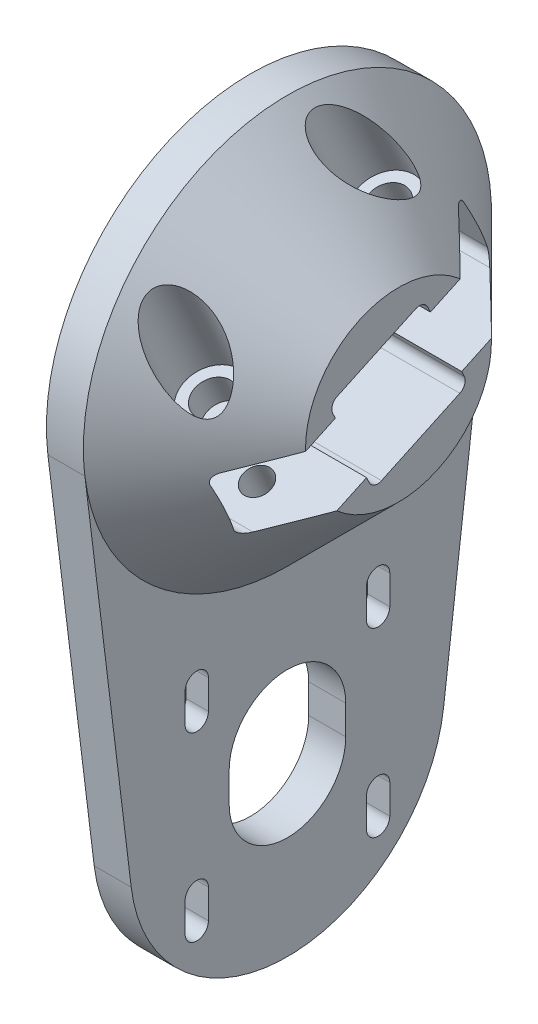
SolidWorks part; units mm, degrees
ref_plane "Front Plane" through (0, 0, 0) normal (0, 0, 1) x (1, 0, 0)
ref_plane "Top Plane" through (0, 0, 0) normal (0, 1, 0) x (1, 0, 0)
ref_plane "Right Plane" through (0, 0, 0) normal (1, 0, 0) x (0, 0, -1)
sketch "Sketch1" plane through (0, 0, 0) normal (1, 0, 0) x (0, 0, -1)
  line L0 (4.3532, 11.9603) -> (-11.9603, 4.3532)
  line L1 (4.3532, 11.9603) -> (11.9603, -4.3532)
  line L2 (-11.9603, 4.3532) -> (-4.3532, -11.9603)
  line L3 (11.9603, -4.3532) -> (-4.3532, -11.9603)
  line L4 (4.3532, 11.9603) -> (-4.3532, -11.9603) construction
  line L5 (-11.9603, 4.3532) -> (11.9603, -4.3532) construction
  line L6 (0, 0) -> (0, -63.5) construction
  line L7 (-34.7419, -4.2424) -> (-26.8009, -69.2727)
  line L8 (26.8009, -69.2727) -> (34.7419, -4.2424)
  line L9 (0, -63.5) -> (0, -103.9417) construction
  arc A0 (34.7419, -4.2424) -> (-34.7419, -4.2424) centre (0, 0) ccw
  arc A1 (-26.8009, -69.2727) -> (26.8009, -69.2727) centre (0, -66) ccw
  dimension "D1" = 2.5
  dimension "D2" = 70
  dimension "D6" = 63.5
  dimension "D7" = 27
  dimension "D8" = 0
  dimension "D3" = 18
  dimension "D4" = 18
  dimension "D5" = 25
extrude "Boss-Extrude1" add sketch "Sketch1" along normal blind 6.35 contours L7 A0 L1 L3 L2 L0 region at (0, -27.7152, 0)
sketch "Sketch17" plane through (0, 0, 0) normal (-1, 0, 0) x (0, 0, 1)
  line L2 (-34.7419, -4.2424) -> (-26.8009, -69.2727)
  line L3 (26.8009, -69.2727) -> (34.7419, -4.2424)
  line L4 (-34.7419, -4.2424) -> (-26.8009, -69.2727)
  line L6 (26.8009, -69.2727) -> (34.7419, -4.2424)
  arc A2 (-26.8009, -69.2727) -> (26.8009, -69.2727) centre (0, -66) ccw
  arc A3 (-26.8009, -69.2727) -> (26.8009, -69.2727) centre (0, -66) ccw
  arc A4 (34.7419, -4.2424) -> (-34.7419, -4.2424) centre (0, 0) ccw
  arc A8 (34.7419, -4.2424) -> (-34.7419, -4.2424) centre (0, 0) ccw
  dimension "D1" = 0
sketch "Sketch20" plane through (6.35, 0, 0) normal (1, 0, 0) x (0, 0, -1)
  circle A0 centre (0, 0) radius 35
extrude "Boss-Extrude5" add sketch "Sketch20" along normal blind 19.05
sketch "Sketch21" plane through (0, 0, 0) normal (-1, 0, 0) x (0, 0, 1)
  line L0 (-24.435, 4.3878) -> (-10.8404, -1.9515)
  line L1 (11.9603, 4.3532) -> (4.3532, -11.9603) construction
  line L3 (-4.3532, 11.9603) -> (-11.9603, -4.3532) construction
  line L4 (-4.3532, 11.9603) -> (11.9603, 4.3532) construction
  line L5 (11.9603, 4.3532) -> (10.8404, 1.9515)
  line L7 (-4.3532, 11.9603) -> (-5.4731, 9.5586)
  line L8 (-4.3532, 11.9603) -> (11.9603, 4.3532)
  line L9 (-21.7514, 10.1428) -> (-25.3766, 11.8333) construction
  line L10 (19.0678, -15.8979) -> (5.4731, -9.5586)
  line L11 (19.0678, -15.8979) -> (24.435, -4.3878)
  line L12 (-24.435, 4.3878) -> (-19.0678, 15.8979)
  line L13 (24.435, -4.3878) -> (10.8404, 1.9515)
  line L16 (4.3532, -11.9603) -> (5.4731, -9.5586)
  line L17 (-11.9603, -4.3532) -> (-10.8404, -1.9515)
  line L18 (11.9603, 4.3532) -> (-4.3532, 11.9603)
  line L21 (-10.8404, -1.9515) -> (-11.9603, -4.3532)
  line L24 (-10.8404, -1.9515) -> (-24.435, 4.3878)
  line L27 (-5.4731, 9.5586) -> (-4.3532, 11.9603)
  line L29 (-5.4731, 9.5586) -> (-19.0678, 15.8979)
  line L30 (5.4731, -9.5586) -> (4.3532, -11.9603)
  line L31 (10.8404, 1.9515) -> (11.9603, 4.3532)
  line M13 (-11.9603, -4.3532) -> (-4.3532, 11.9603)
  line M14 (-4.3532, 11.9603) -> (11.9603, 4.3532)
  line M15 (11.9603, 4.3532) -> (4.3532, -11.9603)
  line M16 (4.3532, -11.9603) -> (-11.9603, -4.3532)
  dimension "D1" = 15
  dimension "D2" = 12.7
extrude "Cut-Extrude14" cut sketch "Sketch21" against normal through all contours L29 L12 L0 M13 | M13 M16 M15 M14 | L11 L13 L10 M15 region at (0, 6.9732, -14.9541) region at (0, 0, 0) region at (0, -6.9732, 14.9541)
chamfer "Chamfer1" distance 19.05 angle 45 1 edges at (25.4, 0, -35)
sketch "Sketch22" plane through (0, 5.7551, 2.6836) normal (0, -0.9063, -0.4226) x (-1, 0, 0)
  line L0 (-25.4, -9) -> (0, -9) construction
  line L1 (-25.4, -9) -> (-25.4, -14.6315) construction
  circle A0 centre (-13.4, -16.5) radius 3.175
  dimension "D2" = 12
  dimension "D3" = 6.35
  dimension "D1" = 7.5
extrude "Cut-Extrude15" cut sketch "Sketch22" against normal through all
ref_plane "Plane1" through (0, 10.2866, 4.7967) normal (0, -0.9063, -0.4226) x (-1, 0, 0)
sketch "Sketch24" plane through (0, 10.2866, 4.7967) normal (0, -0.9063, -0.4226) x (-1, 0, 0)
  circle A0 centre (-13.4, -16.5) radius 5
  dimension "D1" = 10
extrude "Cut-Extrude16" cut sketch "Sketch24" against normal through all
sketch "Sketch25" plane through (0, -5.7551, -2.6836) normal (0, 0.9063, 0.4226) x (1, 0, 0)
  circle A0 centre (13.4, -16.5) radius 3.175 construction
  circle A1 centre (13.4, -16.5) radius 3.175
  circle A2 centre (13.4, -16.5) radius 2.3813
  dimension "D1" = 0.7937
extrude "Cut-Extrude17" cut sketch "Sketch25" against normal blind 10 contours A2 region at (13.4, -12.7283, 12.2705)
ref_plane "Plane2" through (0, 0, 0) normal (0, 0.4226, -0.9063) x (-1, 0, 0)
mirror "Mirror1" about plane through (0, 0, 0) normal (0, 0.4226, -0.9063) of "Cut-Extrude15", "Cut-Extrude17", "Cut-Extrude16"
sketch "Sketch19" plane through (6.35, 0, 0) normal (1, 0, 0) x (0, 0, -1)
  line L0 (0, -65.325) -> (0, -60.325)
  line L1 (0, -60.325) -> (15.5563, -44.7687) construction
  line L2 (15.5563, -49.7687) -> (15.5563, -44.7687) construction
  line L3 (13.5563, -49.7687) -> (13.5563, -44.7687)
  line L4 (17.5563, -49.7687) -> (17.5563, -44.7687)
  line L5 (-10, -65.325) -> (-10, -60.325)
  line L6 (10, -65.325) -> (10, -60.325)
  line L7 (0, -62.825) -> (7.4061, -62.825) construction
  line L8 (15.5563, -49.7687) -> (0, -65.325) construction
  line L9 (17.5563, -75.8813) -> (17.5563, -80.8813)
  line L10 (13.5563, -75.8813) -> (13.5563, -80.8813)
  line L11 (-17.5563, -49.7687) -> (-17.5563, -44.7687)
  line L12 (-13.5563, -49.7687) -> (-13.5563, -44.7687)
  line L13 (-13.5563, -75.8813) -> (-13.5563, -80.8813)
  line L14 (-17.5563, -75.8813) -> (-17.5563, -80.8813)
  line L15 (-15.5563, -49.7687) -> (0, -65.325) construction
  line L16 (0, -65.325) -> (-15.5563, -80.8813) construction
  line L17 (0, -65.325) -> (15.5563, -80.8813) construction
  arc A2 (-10, -65.325) -> (10, -65.325) centre (0, -65.325) ccw
  arc A3 (17.5563, -80.8813) -> (13.5563, -80.8813) centre (15.5563, -80.8813) cw
  arc A4 (13.5563, -75.8813) -> (17.5563, -75.8813) centre (15.5563, -75.8813) cw
  arc A6 (17.5563, -44.7687) -> (13.5563, -44.7687) centre (15.5563, -44.7687) ccw
  arc A7 (13.5563, -49.7687) -> (17.5563, -49.7687) centre (15.5563, -49.7687) ccw
  arc A8 (-17.5563, -44.7687) -> (-13.5563, -44.7687) centre (-15.5563, -44.7687) cw
  arc A9 (10, -60.325) -> (-10, -60.325) centre (0, -60.325) ccw
  arc A10 (-13.5563, -49.7687) -> (-17.5563, -49.7687) centre (-15.5563, -49.7687) cw
  arc A11 (-13.5563, -75.8813) -> (-17.5563, -75.8813) centre (-15.5563, -75.8813) ccw
  arc A13 (-17.5563, -80.8813) -> (-13.5563, -80.8813) centre (-15.5563, -80.8813) ccw
  point P8 (0, -62.825)
  dimension "D1" = 60.325
  dimension "D3" = 22
  dimension "D5" = 4
  dimension "D6" = 5
  dimension "D4" = 4
  dimension "D2" = 5
  dimension "D7" = 45
extrude "Cut-Extrude18" cut sketch "Sketch19" against normal blind 10 contours L6 A9 L5 A2 | A10 L12 A8 L11 | L14 A13 L13 A11 | A4 L10 A3 L9 | L4 A6 L3 A7 region at (6.35, -62.825, 9.6798) region at (6.35, -78.3813, -15.5563) region at (6.35, -47.2687, 15.5563) region at (6.35, -78.3813, 15.5563)
mirror "Mirror2" about plane through (0, 0, 0) normal (1, 0, 0) of bodies 126
delete or keep bodies "Body-Delete/Keep 1" type delete bodies bodies 127
chamfer "Chamfer2" distance 2.5 angle 45 8 edges at (0, -51.7687, 15.5563) (0, -47.2687, 13.5563) (0, -42.7687, 15.5563) (0, -47.2687, 17.5563) (0, -51.7687, -15.5563) (0, -47.2687, -17.5563) (0, -47.2687, -13.5563) (0, -42.7687, -15.5563)
sketch "Sketch26" plane through (0, 0, 0) normal (-1, 0, 0) x (0, 0, 1)
  line L0 (11.5536, -63.5674) -> (27.2473, -7.6467)
  line L1 (0, 0) -> (0, -60.325) construction
  circle A0 centre (0, -60.325) radius 12
  circle A1 centre (0, 0) radius 28.3
  dimension "D1" = 24
  dimension "D2" = 56.6
fillet "Fillet1" radius 1.5875 8 edges at (12.7, -4.3532, -11.9603) (8.2621, 4.3878, -24.435) (12.7, 11.9603, -4.3532) (8.2621, 15.8979, -19.0678) (8.2621, -4.3878, 24.435) (12.7, 4.3532, 11.9603) (12.7, -11.9603, 4.3532) (8.2621, -15.8979, 19.0678)
sketch "Sketch27" plane through (6.35, 0, 0) normal (1, 0, 0) x (0, 0, -1)
  arc A0 (-26.8009, -69.2727) -> (26.8009, -69.2727) centre (0, -66) ccw construction
  arc A1 (34.7419, -4.2424) -> (-34.7419, -4.2424) centre (0, 0) ccw construction
  point P0 (0, -93)
  point P1 (0, 35)
  point P5 (-34.7419, -4.2424)
  point P9 (35, 0)
equation "\".75i\"=14.27"
